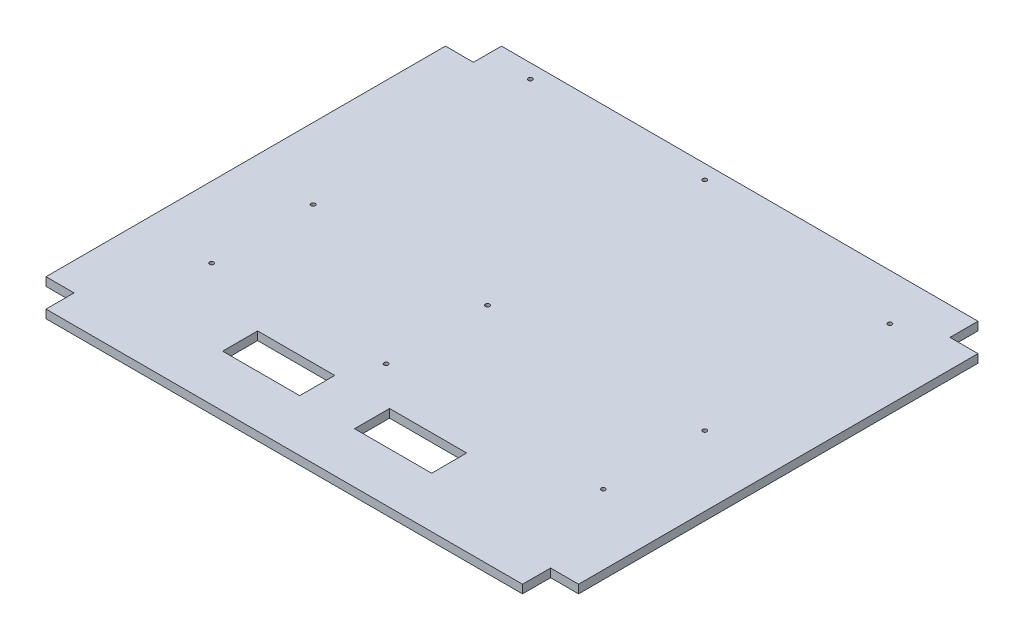
SolidWorks part; units mm, degrees
ref_plane "Front" through (0, 0, 0) normal (0, 0, 1) x (1, 0, 0)
ref_plane "Top" through (0, 0, 0) normal (0, 1, 0) x (1, 0, 0)
ref_plane "Right" through (0, 0, 0) normal (1, 0, 0) x (0, 0, -1)
sketch "Base Plate" plane through (0, 0, 0) normal (0, 1, 0) x (1, 0, 0)
  line L0 (-190, 162.5) -> (190, -162.5) construction
  line L1 (-190, 162.5) -> (190, 162.5)
  line L2 (-190, 162.5) -> (-190, -162.5)
  line L3 (-190, -162.5) -> (190, -162.5)
  line L4 (190, 162.5) -> (190, -162.5)
  line L5 (149, 162.5) -> (149, -162.5) construction
  line L6 (-155.8, 162.5) -> (-155.8, -162.5) construction
  line L7 (-155.8, -81.34) -> (149, -81.34) construction
  line L8 (-139.29, 162.5) -> (-139.29, -81.34) construction
  line L9 (14, -101.34) -> (69, -101.34)
  line L10 (14, -101.34) -> (14, -126.34)
  line L11 (14, -126.34) -> (69, -126.34)
  line L12 (69, -101.34) -> (69, -126.34)
  line L13 (-26, -100.5) -> (-81, -100.5)
  line L14 (-26, -100.5) -> (-26, -125.5)
  line L15 (-26, -125.5) -> (-81, -125.5)
  line L16 (-81, -100.5) -> (-81, -125.5)
  line L17 (-155.8, -74.99) -> (149, -74.99) construction
  line L18 (-155.8, 152.34) -> (149, 152.34) construction
  line L19 (-155.8, -2.6) -> (149, -2.6) construction
  line L20 (-14.83, 162.5) -> (-14.83, -81.34) construction
  line L21 (140.11, 162.5) -> (140.11, -81.34) construction
  circle A0 centre (-139.29, -74.99) radius 1.5
  circle A3 centre (-14.83, -2.6) radius 1.5
  circle A4 centre (-139.29, -2.6) radius 1.5
  circle A5 centre (-139.29, 152.34) radius 1.5
  circle A6 centre (-14.83, 152.34) radius 1.5
  circle A7 centre (-14.83, -74.99) radius 1.5
  circle A8 centre (140.11, -74.99) radius 1.5
  circle A9 centre (140.11, -2.6) radius 1.5
  circle A10 centre (140.11, 129.48) radius 1.5
  circle A11 centre (-180, -152.5) radius 2.5
  circle A12 centre (180, -152.5) radius 2.5
  circle A13 centre (-180, 152.5) radius 2.5
  circle A14 centre (180, 152.5) radius 2.5
  dimension "D14" = 3
  dimension "D15" = 10.16
  dimension "D22" = 5
  dimension "D1" = 325
  dimension "D2" = 380
  dimension "D3" = 41
  dimension "D4" = 304.8
  dimension "D5" = 154.94
  dimension "D6" = 243.84
  dimension "D7" = 80
  dimension "D8" = 55
  dimension "D9" = 25
  dimension "D10" = 20
  dimension "D11" = 40
  dimension "D12" = 55
  dimension "D13" = 16.51
  dimension "D16" = 279.4
  dimension "D17" = 227.33
  dimension "D18" = 124.46
  dimension "D19" = 22.86
  dimension "D20" = 10
  dimension "D21" = 10
  dimension "D23" = 10
  dimension "D24" = 10
  dimension "D25" = 10
  dimension "D26" = 10
  dimension "D27" = 10
  dimension "D28" = 10
extrude "Boss-Extrude1" add sketch "Base Plate" along normal blind 6
sketch "Sketch1" plane through (0, 6, 0) normal (0, 1, 0) x (1, 0, 0)
  line L1 (-190, 162.5) -> (-170, 162.5)
  line L2 (-190, 162.5) -> (-190, 142.5)
  line L3 (-190, 142.5) -> (-170, 142.5)
  line L4 (-170, 162.5) -> (-170, 142.5)
  line L5 (190, 162.5) -> (170, 162.5)
  line L6 (190, 162.5) -> (190, 142.5)
  line L7 (190, 142.5) -> (170, 142.5)
  line L8 (170, 162.5) -> (170, 142.5)
  line L9 (190, -162.5) -> (170, -162.5)
  line L10 (190, -162.5) -> (190, -142.5)
  line L11 (190, -142.5) -> (170, -142.5)
  line L12 (170, -162.5) -> (170, -142.5)
  line L13 (-190, -162.5) -> (-170, -162.5)
  line L14 (-190, -162.5) -> (-190, -142.5)
  line L15 (-190, -142.5) -> (-170, -142.5)
  line L16 (-170, -162.5) -> (-170, -142.5)
  dimension "D1" = 20
  dimension "D2" = 20
  dimension "D3" = 20
  dimension "D4" = 20
extrude "Cut-Extrude1" cut sketch "Sketch1" against normal blind 10
